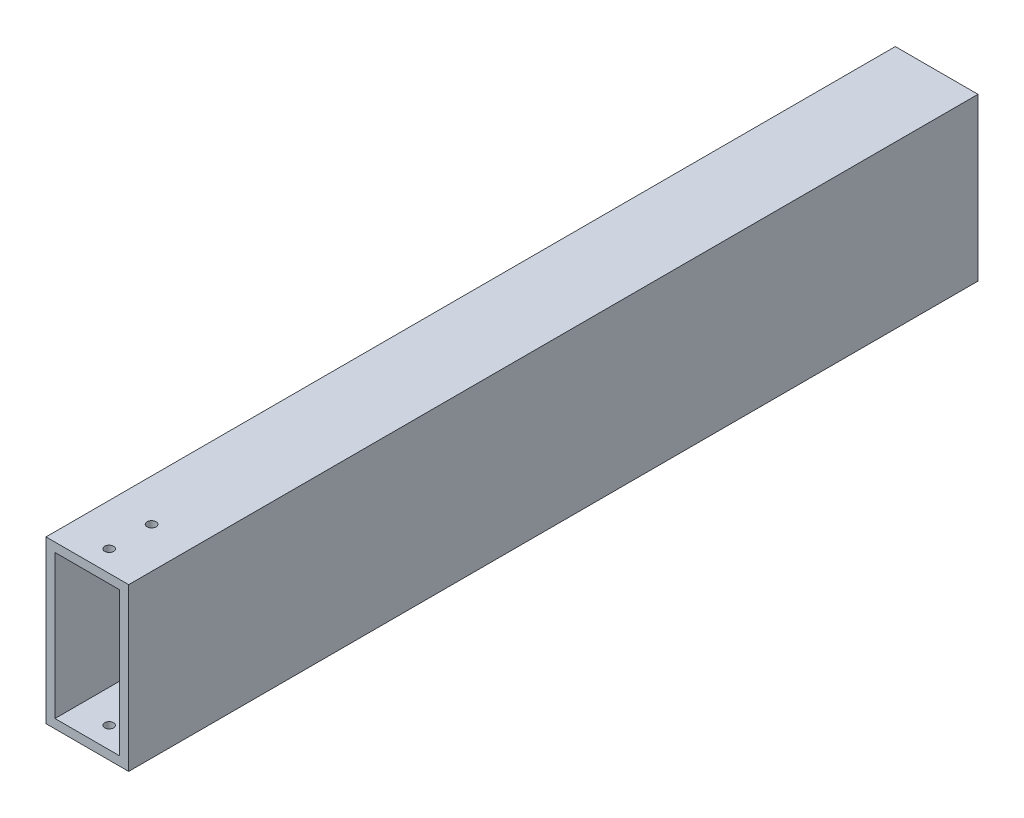
SolidWorks part; units mm, degrees
ref_plane "Front Plane" through (0, 0, 0) normal (0, 0, 1) x (1, 0, 0)
ref_plane "Top Plane" through (0, 0, 0) normal (0, 1, 0) x (1, 0, 0)
ref_plane "Right Plane" through (0, 0, 0) normal (1, 0, 0) x (0, 0, -1)
sketch "Sketch1" plane through (0, 0, 0) normal (0, 0, 1) x (1, 0, 0)
  line L0 (-6.35, -6.35) -> (-6.35, 107.95)
  line L1 (0, 0) -> (45.72, 0) construction
  line L2 (0, 0) -> (0, 101.6) construction
  line L3 (0, 101.6) -> (45.72, 101.6) construction
  line L4 (45.72, 0) -> (45.72, 101.6) construction
  line L5 (-6.35, 107.95) -> (52.07, 107.95)
  line L6 (52.07, -6.35) -> (52.07, 107.95)
  line L7 (-6.35, -6.35) -> (52.07, -6.35)
  dimension "D1" = 45.72
  dimension "D2" = 101.6
  dimension "D3" = 6.35
extrude "Boss-Extrude1" add sketch "Sketch1" against normal blind 600
sketch "Sketch2" plane through (0, 0, 0) normal (0, 0, 1) x (1, 0, 0)
  line L0 (45.72, 101.6) -> (0, 101.6)
  line L1 (0, 101.6) -> (0, 0)
  line L2 (0, 0) -> (45.72, 0)
  line L3 (45.72, 0) -> (45.72, 101.6)
  line L4 (-6.35, -6.35) -> (52.07, -6.35)
  line L5 (52.07, -6.35) -> (52.07, 107.95)
  line L6 (52.07, 107.95) -> (-6.35, 107.95)
  line L7 (-6.35, 107.95) -> (-6.35, -6.35)
  line L8 (-6.35, -6.35) -> (52.07, -6.35) construction
  line L9 (52.07, -6.35) -> (52.07, 107.95) construction
  line L10 (52.07, 107.95) -> (-6.35, 107.95) construction
  line L11 (-6.35, 107.95) -> (-6.35, -6.35) construction
  point P8 (0, 0)
  dimension "D1" = 0
  dimension "D2" = 6.35
extrude "Cut-Extrude1" cut sketch "Sketch2" against normal blind 60
sketch "Sketch3" plane through (0, -6.35, 0) normal (0, -1, 0) x (1, 0, 0)
  circle A3 centre (23.241, -45) radius 3.175
  circle A4 centre (23.241, -45) radius 3.175
  circle A5 centre (23.241, -15) radius 3.175
  circle A6 centre (23.241, -15) radius 3.175
  dimension "D2" = 0
  dimension "D3" = 0
extrude "Cut-Extrude2" cut sketch "Sketch3" against normal through all
sketch "Sketch4" plane through (-6.35, 0, 0) normal (-1, 0, 0) x (0, 0, 1)
  line L0 (-600, 50.8) -> (0, 50.8) construction
  line L1 (-550, 50.8) -> (-50, 50.8) construction
  line L2 (-550, 45.8) -> (-50, 45.8)
  line L3 (-550, 55.8) -> (-50, 55.8)
  line L4 (0, -6.35) -> (0, 107.95)
  line L5 (0, 107.95) -> (-600, 107.95)
  line L6 (-600, 107.95) -> (-600, -6.35)
  line L7 (-600, -6.35) -> (0, -6.35)
  line L8 (0, -6.35) -> (0, 107.95) construction
  line L9 (0, 107.95) -> (-600, 107.95) construction
  line L10 (-600, 107.95) -> (-600, -6.35) construction
  line L11 (-600, -6.35) -> (0, -6.35) construction
  line L13 (-50, 55.8) -> (-550, 55.8)
  line L14 (-50, 55.8) -> (-50, 45.8)
  line L15 (-50, 45.8) -> (-550, 45.8)
  line L16 (-550, 55.8) -> (-550, 45.8)
  point P6 (-50, 50.8)
  point P7 (-550, 50.8)
  dimension "D2" = 500
  dimension "D3" = 50
  dimension "D1" = 0
  dimension "D4" = 5
  dimension "D5" = 5
extrude "Cut-Extrude3" cut sketch "Sketch4" against normal blind 5 contours L3 L16 L2 L14 region at (-6.35, 50.8, -300)
